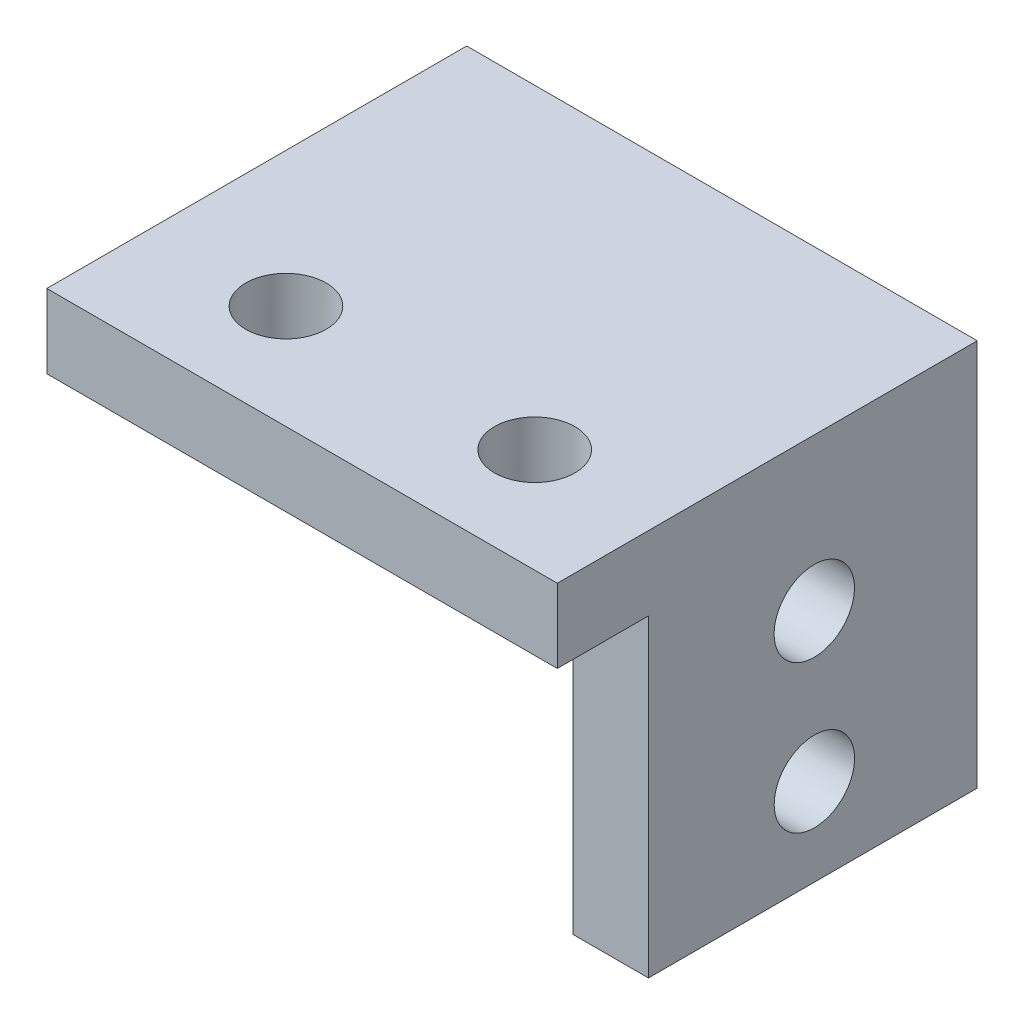
SolidWorks part; units mm, degrees
ref_plane "Front" through (0, 0, 0) normal (0, 0, 1) x (1, 0, 0)
ref_plane "Top" through (0, 0, 0) normal (0, 1, 0) x (1, 0, 0)
ref_plane "Right" through (0, 0, 0) normal (1, 0, 0) x (0, 0, -1)
sketch "Sketch1" plane through (0, 0, 0) normal (0, 1, 0) x (1, 0, 0)
  line L1 (0, 0) -> (20.32, 0)
  line L2 (0, 0) -> (0, 20.32)
  line L3 (0, 20.32) -> (20.32, 20.32)
  line L4 (20.32, 0) -> (20.32, 20.32)
  dimension "D1" = 20.32
  dimension "D2" = 20.32
extrude "Boss-Extrude1" add sketch "Sketch1" along normal blind 3
sketch "Sketch2" plane through (20.32, 0, 0) normal (1, 0, 0) x (0, 0, -1)
  line L0 (16.714, -413.574) -> (16.714, 10.926) construction
  line L1 (16.714, 3.0402) -> (3.6282, 3.0402)
  line L2 (16.714, 3.0402) -> (16.714, -12.4821)
  line L3 (16.714, -12.4821) -> (3.6282, -12.4821)
  line L4 (3.6282, 3.0402) -> (3.6282, -12.4821)
  line L5 (3.6282, 20.926) -> (3.6282, -423.574) construction
extrude "Boss-Extrude2" add sketch "Sketch2" against normal blind 3
sketch "Sketch5" plane through (0, 3.0402, 0) normal (0, 1, 0) x (1, 0, 0)
  line L1 (-2.5119, 22.0495) -> (29.0757, 22.0495)
  line L2 (-2.5119, 22.0495) -> (-2.5119, -3.5135)
  line L3 (-2.5119, -3.5135) -> (29.0757, -3.5135)
  line L4 (29.0757, 22.0495) -> (29.0757, -3.5135)
extrude "Cut-Extrude1" cut sketch "Sketch5" against normal blind 0.1
sketch "Sketch6" plane through (0, 0, 0) normal (0, -1, 0) x (-1, 0, 0)
  line L1 (0, 20.32) -> (-20.32, 20.32)
  line L2 (0, 20.32) -> (0, 16.714)
  line L3 (0, 16.714) -> (-20.32, 16.714)
  line L4 (-20.32, 20.32) -> (-20.32, 16.714)
extrude "Cut-Extrude2" cut sketch "Sketch6" against normal blind 10
sketch "Sketch7" plane through (0, 2.9402, 0) normal (0, 1, 0) x (1, 0, 0)
  circle A0 centre (5.37, 4.15) radius 1.6
  circle A1 centre (15.27, 4.15) radius 1.6
extrude "Cut-Extrude3" cut sketch "Sketch7" against normal blind 10
sketch "Sketch8" plane through (17.32, 0, 0) normal (-1, 0, 0) x (0, 0, 1)
  line L1 (-3.6282, 0) -> (-3.6282, -12.4821) construction
  circle A0 centre (-10.2322, -9.0065) radius 1.6
  circle A1 centre (-10.2282, -3.1271) radius 1.6
  dimension "D1" = 6.604
  dimension "D2" = 6.6
extrude "Cut-Extrude4" cut sketch "Sketch8" against normal blind 10
